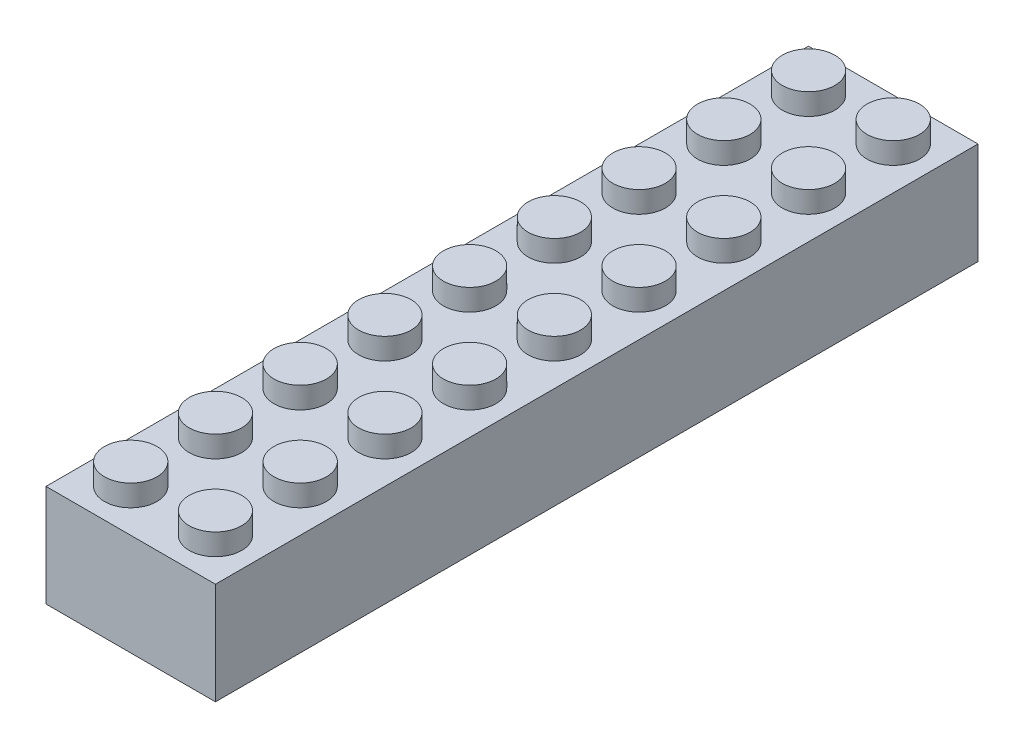
SolidWorks part; units mm, degrees
ref_plane "Front Plane" through (0, 0, 0) normal (0, 0, 1) x (1, 0, 0)
ref_plane "Top Plane" through (0, 0, 0) normal (0, 1, 0) x (1, 0, 0)
ref_plane "Right Plane" through (0, 0, 0) normal (1, 0, 0) x (0, 0, -1)
sketch "stencil" plane through (0, 0, 0) normal (0, 1, 0) x (1, 0, 0)
  line L2 (7.9, 71.1) -> (7.9, 0) construction
  line L29 (14.3, 1.5) -> (1.5, 1.5)
  line L30 (15.8, 71.1) -> (0, 71.1)
  line L32 (15.8, 71.1) -> (15.8, 0)
  line L34 (15.8, 0) -> (0, 0)
  line L36 (0, 71.1) -> (0, 0)
  line L37 (7.9, 0) -> (7.9, 71.1) construction
  line L38 (15.8, 35.55) -> (0, 35.55) construction
  line L39 (1.5, 69.6) -> (1.5, 1.5)
  line L40 (14.3, 69.6) -> (1.5, 69.6)
  line L41 (14.3, 69.6) -> (14.3, 1.5)
  circle A40 centre (3.95, 3.95) radius 2.45
  circle A41 centre (7.9, 7.9) radius 3.25
  circle A42 centre (3.95, 11.85) radius 2.45
  circle A43 centre (3.95, 19.75) radius 2.45
  circle A44 centre (3.95, 27.65) radius 2.45
  circle A45 centre (7.9, 15.8) radius 3.25
  circle A46 centre (7.9, 23.7) radius 3.25
  circle A47 centre (7.9, 31.6) radius 3.25
  circle A48 centre (3.95, 35.55) radius 2.45
  circle A49 centre (3.95, 43.45) radius 2.45
  circle A50 centre (3.95, 51.35) radius 2.45
  circle A51 centre (7.9, 39.5) radius 3.25
  circle A52 centre (7.9, 47.4) radius 3.25
  circle A53 centre (3.95, 59.25) radius 2.45
  circle A54 centre (3.95, 67.15) radius 2.45
  circle A55 centre (7.9, 55.3) radius 3.25
  circle A56 centre (7.9, 63.2) radius 3.25
  circle A57 centre (7.9, 7.9) radius 2.45
  circle A58 centre (7.9, 15.8) radius 2.45
  circle A59 centre (7.9, 23.7) radius 2.45
  circle A60 centre (7.9, 31.6) radius 2.45
  circle A61 centre (7.9, 39.5) radius 2.45
  circle A62 centre (7.9, 47.4) radius 2.45
  circle A63 centre (7.9, 55.3) radius 2.45
  circle A64 centre (7.9, 63.2) radius 2.45
  circle A65 centre (11.85, 11.85) radius 2.45
  circle A66 centre (11.85, 19.75) radius 2.45
  circle A67 centre (11.85, 27.65) radius 2.45
  circle A68 centre (11.85, 35.55) radius 2.45
  circle A69 centre (11.85, 43.45) radius 2.45
  circle A70 centre (11.85, 51.35) radius 2.45
  circle A71 centre (11.85, 59.25) radius 2.45
  circle A72 centre (11.85, 67.15) radius 2.45
  circle A73 centre (11.85, 3.95) radius 2.45
  point P1 (0, 0)
  point P6 (3.95, -15.8)
  point P9 (7.9, -15.8)
  point P10 (7.9, -11.85)
  point P13 (3.95, -7.9)
  point P15 (7.9, -7.9)
  point P17 (7.9, -3.95)
  point P18 (3.95, 0)
  point P21 (7.9, 0)
  point P25 (7.9, 3.95)
  point P27 (3.95, 7.9)
  point P28 (7.9, 7.9)
  point P29 (0, -11.85)
  point P30 (0, -7.9)
  point P31 (0, 3.95)
  point P34 (0, -3.95)
  point P35 (3.95, 0)
  point P36 (0, 15.8)
  point P37 (0, 23.7)
  point P38 (7.9, 23.7)
  point P39 (15.8, 23.7)
  point P40 (15.8, 15.8)
  point P41 (15.8, 7.9)
  point P43 (7.9, 0)
  point P48 (11.85, 0)
  point P49 (15.8, 0)
  point P50 (3.95, 3.95)
  point P51 (7.9, 3.95)
  point P52 (11.85, 3.95)
  point P53 (15.8, 3.95)
  point P54 (3.95, 7.9)
  point P55 (7.9, 7.9)
  point P56 (11.85, 7.9)
  point P57 (15.8, 7.9)
  point P58 (3.95, 11.85)
  point P59 (7.9, 11.85)
  point P60 (11.85, 11.85)
  point P61 (15.8, 11.85)
  point P63 (3.95, 15.8)
  point P64 (7.9, 15.8)
  point P65 (11.85, 15.8)
  point P66 (15.8, 15.8)
  point P67 (3.95, 19.75)
  point P68 (7.9, 19.75)
  point P69 (11.85, 19.75)
  point P70 (15.8, 19.75)
  point P71 (3.95, 23.7)
  point P72 (7.9, 23.7)
  point P73 (11.85, 23.7)
  point P75 (15.8, 23.7)
  point P77 (3.95, 27.65)
  point P79 (7.9, 27.65)
  point P81 (11.85, 27.65)
  point P83 (15.8, 27.65)
  point P85 (3.95, 31.6)
  point P87 (7.9, 31.6)
  point P88 (11.85, 31.6)
  point P89 (15.8, 31.6)
  point P90 (0, 3.95)
  point P91 (0, 7.9)
  point P92 (0, 11.85)
  point P93 (0, 15.8)
  point P94 (0, 19.75)
  point P95 (0, 23.7)
  point P96 (0, 27.65)
  point P97 (0, 31.6)
  point P113 (0, 35.55)
  point P114 (3.95, 35.55)
  point P115 (7.9, 35.55)
  point P116 (11.85, 35.55)
  point P117 (15.8, 35.55)
  point P118 (0, 39.5)
  point P119 (3.95, 39.5)
  point P120 (7.9, 39.5)
  point P121 (11.85, 39.5)
  point P122 (15.8, 39.5)
  point P124 (0, 43.45)
  point P125 (3.95, 43.45)
  point P126 (7.9, 43.45)
  point P127 (11.85, 43.45)
  point P128 (15.8, 43.45)
  point P129 (0, 47.4)
  point P130 (3.95, 47.4)
  point P131 (7.9, 47.4)
  point P132 (11.85, 47.4)
  point P133 (15.8, 47.4)
  point P135 (0, 51.35)
  point P136 (3.95, 51.35)
  point P137 (7.9, 51.35)
  point P138 (11.85, 51.35)
  point P139 (15.8, 51.35)
  point P140 (0, 55.3)
  point P141 (3.95, 55.3)
  point P142 (7.9, 55.3)
  point P143 (11.85, 55.3)
  point P144 (15.8, 55.3)
  point P145 (0, 59.25)
  point P146 (3.95, 59.25)
  point P147 (7.9, 59.25)
  point P148 (11.85, 59.25)
  point P149 (15.8, 59.25)
  point P150 (0, 63.2)
  point P151 (3.95, 63.2)
  point P152 (7.9, 63.2)
  point P153 (11.85, 63.2)
  point P154 (15.8, 63.2)
  point P165 (0, 67.15)
  point P166 (3.95, 67.15)
  point P167 (7.9, 67.15)
  point P168 (11.85, 67.15)
  point P169 (15.8, 67.15)
  point P170 (0, 71.1)
  point P171 (3.95, 71.1)
  point P172 (7.9, 71.1)
  point P173 (11.85, 71.1)
  point P174 (15.8, 71.1)
  point P182 (7.9, 35.55)
  dimension "D8" = 4.9
  dimension "D9" = 6.5
  dimension "D3" = 3.95
  dimension "D4" = 3.95
  dimension "D5" = 15.8
  dimension "D6" = 71.1
  dimension "D7" = 0.8
  dimension "D10" = 1.5
  dimension "D1" = 5
  dimension "D2" = 19
sketch "Sketch1" plane through (0, 0, 0) normal (0, 1, 0) x (1, 0, 0)
  line L1 (15.8, 71.1) -> (0, 71.1)
  line L2 (15.8, 71.1) -> (15.8, 0)
  line L3 (15.8, 0) -> (0, 0)
  line L4 (0, 71.1) -> (0, 0)
  line L5 (7.9, 0) -> (7.9, 71.1) construction
  line L6 (15.8, 35.55) -> (0, 35.55) construction
  point P0 (7.9, 35.55)
extrude "Boss-Extrude1" add sketch "Sketch1" along normal mid plane 9.5
sketch "Sketch2" plane through (0, 4.75, 0) normal (0, 1, 0) x (1, 0, 0)
  line L0 (0, 71.1) -> (0, 0) construction
  circle A0 centre (3.95, 3.95) radius 2.45
  circle A1 centre (11.85, 3.95) radius 2.45
  circle A2 centre (11.85, 11.85) radius 2.45
  circle A3 centre (3.95, 11.85) radius 2.45
  circle A4 centre (3.95, 19.75) radius 2.45
  circle A5 centre (3.95, 27.65) radius 2.45
  circle A6 centre (11.85, 27.65) radius 2.45
  circle A7 centre (11.85, 35.55) radius 2.45
  circle A8 centre (3.95, 35.55) radius 2.45
  circle A9 centre (3.95, 43.45) radius 2.45
  circle A10 centre (11.85, 43.45) radius 2.45
  circle A11 centre (3.95, 51.35) radius 2.45
  circle A12 centre (11.85, 51.35) radius 2.45
  circle A13 centre (3.95, 59.25) radius 2.45
  circle A14 centre (11.85, 59.25) radius 2.45
  circle A15 centre (3.95, 67.15) radius 2.45
  circle A16 centre (11.85, 67.15) radius 2.45
  circle A17 centre (3.95, 3.95) radius 2.45 construction
  circle A18 centre (11.85, 19.75) radius 2.45
  circle A19 centre (11.85, 19.75) radius 2.45 construction
extrude "Boss-Extrude2" add sketch "Sketch2" along normal blind 2
sketch "Sketch3" plane through (0, -4.75, 0) normal (0, -1, 0) x (1, 0, 0)
  line L1 (14.3, -1.5) -> (1.5, -1.5)
  line L2 (14.3, -1.5) -> (14.3, -69.6)
  line L3 (14.3, -69.6) -> (1.5, -69.6)
  line L4 (1.5, -1.5) -> (1.5, -69.6)
  line L5 (7.9, -69.6) -> (7.9, -1.5) construction
  line L6 (14.3, -35.55) -> (1.5, -35.55) construction
  point P0 (7.9, -35.55)
extrude "Cut-Extrude1" cut sketch "Sketch3" against normal blind 4
sketch "Sketch4" plane through (0, -0.75, 0) normal (0, -1, 0) x (1, 0, 0)
  circle A0 centre (7.9, -63.2) radius 3.25
  circle A1 centre (7.9, -55.3) radius 3.25
  circle A2 centre (7.9, -47.4) radius 3.25
  circle A3 centre (7.9, -39.5) radius 3.25
  circle A4 centre (7.9, -31.6) radius 3.25
  circle A5 centre (7.9, -23.7) radius 3.25
  circle A6 centre (7.9, -15.8) radius 3.25
  circle A7 centre (7.9, -7.9) radius 3.25
  circle A8 centre (7.9, -7.9) radius 2.45
  circle A10 centre (7.9, -15.8) radius 2.45
  circle A11 centre (7.9, -23.7) radius 2.45
  circle A12 centre (7.9, -31.6) radius 2.45
  circle A13 centre (7.9, -39.5) radius 2.45
  circle A14 centre (7.9, -47.4) radius 2.45
  circle A15 centre (7.9, -55.3) radius 2.45
  circle A16 centre (7.9, -63.2) radius 2.45
  circle A17 centre (7.9, -63.2) radius 2.45 construction
  circle A18 centre (7.9, -63.2) radius 3.25 construction
extrude "Boss-Extrude3" add sketch "Sketch4" along normal up to surface (4 mm away) up to face at (7.9, -4.75, -35.55)
equation "\"t\"= 0'tolerance"
equation "\"D5@stencil\"=15.80-\"t\""
equation "\"D10@stencil\"=1.5-\"t\""
equation "\"D6@stencil\"=71.10mm-\"t\""
equation "\"D9@stencil\"=6.50-\"t\""
equation "\"D1@Boss-Extrude1\"=9.5-\"t\""
